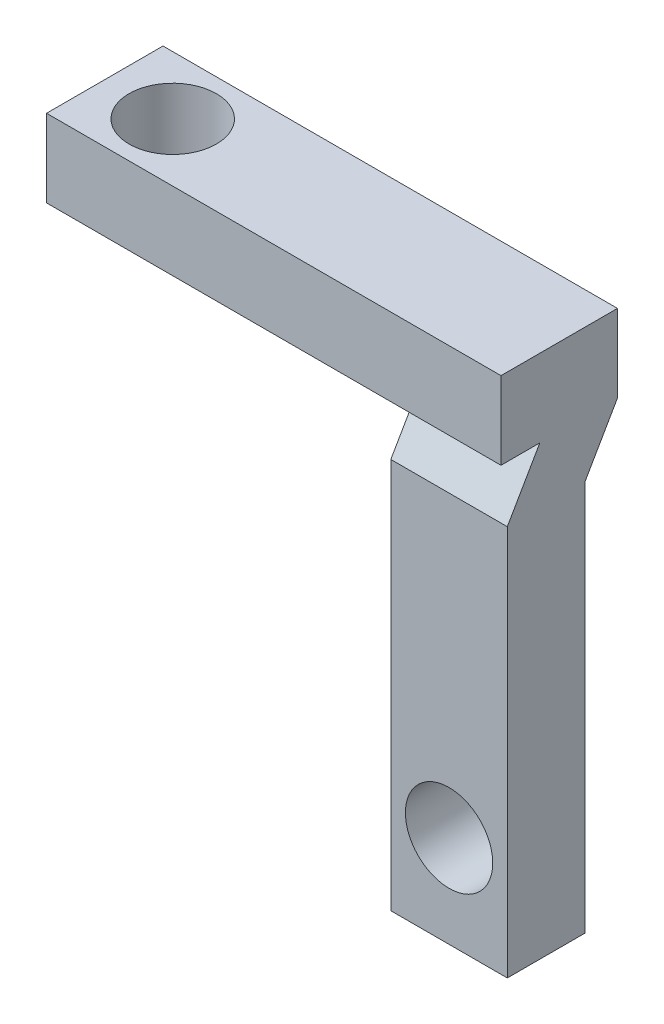
SolidWorks part; units mm, degrees
note: The reader was unsure of these and kept them because the rebuilt part matched: shared geometry of "Sketch1<3>".
ref_plane "Front Plane" through (0, 0, 0) normal (0, 0, 1) x (1, 0, 0)
ref_plane "Top Plane" through (0, 0, 0) normal (0, 1, 0) x (1, 0, 0)
ref_plane "Right Plane" through (0, 0, 0) normal (1, 0, 0) x (0, 0, -1)
sketch "Sketch1" plane through (0, 0, 0) normal (1, 0, 0) x (0, 0, -1)
  line L0 (471.916, 0) -> (483.916, 0)
  line L1 (772.2979, 0) -> (-772.2979, 0) construction
  line L2 (483.916, -8) -> (483.916, 0)
  line L3 (471.916, 0) -> (471.916, -8)
  line L4 (471.916, -8) -> (475.916, -8)
  line L7 (475.916, -8) -> (483.916, -8)
  line L8 (480.566, -54.07) -> (472.566, -54.07)
  line L10 (472.566, -54.07) -> (472.566, -13.8024)
  line L11 (480.566, -54.07) -> (480.566, -13.8024)
  line L14 (475.916, -8) -> (472.566, -13.8024)
  line L16 (483.916, -8) -> (480.566, -13.8024)
  dimension "D1" = 3.35
  dimension "D2" = 8
  dimension "D3" = 12
  dimension "D4" = 8
  dimension "D5" = 60
  dimension "D6" = 60
extrude "Boss-Extrude1" add sketch "Sketch1" against normal blind 12
extrude "Boss-Extrude2" add sketch "Sketch1<3>" against normal blind 46.82 contours L4 L7 L2 L0 L3
sketch "Sketch1<3>" plane through (0, 0, 0) normal (1, 0, 0) x (0, 0, -1) same geometry as "Sketch1"
sketch "Sketch3" plane through (0, -8, 0) normal (0, -1, 0) x (1, 0, 0)
  line L0 (-46.82, -477.916) -> (-12, -477.916) construction
  line L1 (-46.82, -471.916) -> (-46.82, -483.916) construction
  line L3 (-46.82, -471.916) -> (-46.82, -483.916) construction
  line L4 (-12, -475.916) -> (-12, -483.916) construction
  circle A0 centre (-39.82, -477.916) radius 4.5
  dimension "D1" = 7
extrude "Cut-Extrude2" cut sketch "Sketch3" along direction (0, -1, 0) on the side against the normal up to next (8 mm away)
sketch "Sketch5" plane through (0, 0, -472.566) normal (0, 0, 1) x (1, 0, 0)
  line L0 (-6, -54.07) -> (-6, -13.8024) construction
  line L1 (-12, -54.07) -> (0, -54.07) construction
  line L2 (-12, -13.8024) -> (0, -13.8024) construction
  circle A0 centre (-6, -44.57) radius 4.5
  dimension "D1" = 9.5
extrude "Cut-Extrude4" cut sketch "Sketch5" against normal up to surface (8 mm away) up to face at (-6, -33.9362, -480.566)
